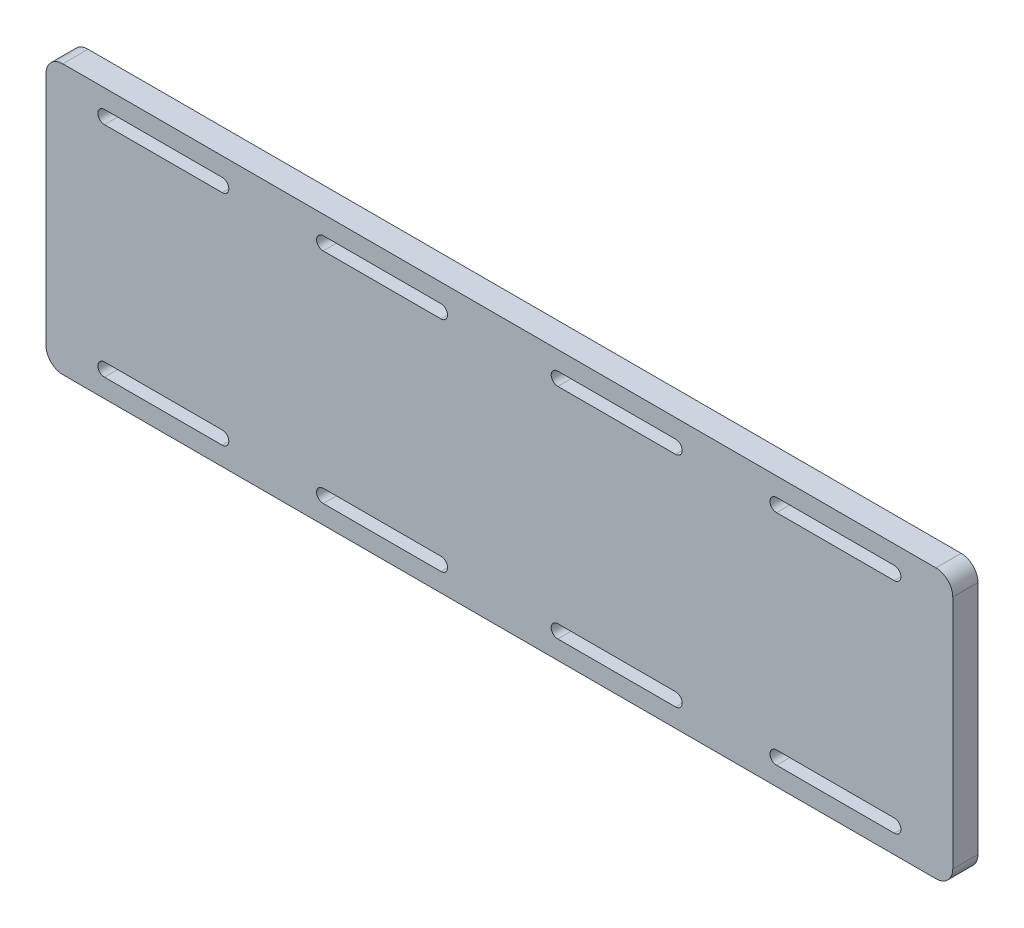
SolidWorks part; units mm, degrees
ref_plane "Front Plane" through (0, 0, 0) normal (0, 0, 1) x (1, 0, 0)
ref_plane "Top Plane" through (0, 0, 0) normal (0, 1, 0) x (1, 0, 0)
ref_plane "Right Plane" through (0, 0, 0) normal (1, 0, 0) x (0, 0, -1)
sketch "Sketch1" plane through (0, 0, 0) normal (0, 0, 1) x (1, 0, 0)
  line L1 (-171.0944, 50.8) -> (171.0944, 50.8)
  line L2 (-171.0944, 50.8) -> (-171.0944, -50.8)
  line L3 (-171.0944, -50.8) -> (171.0944, -50.8)
  line L4 (171.0944, 50.8) -> (171.0944, -50.8)
  line L5 (-171.0944, 50.8) -> (171.0944, -50.8) construction
  line L6 (-171.0944, -50.8) -> (171.0944, 50.8) construction
  point P0 (0, 0)
  dimension "D1" = 101.6
  dimension "D2" = 342.1888
extrude "Boss-Extrude1" add sketch "Sketch1" along normal blind 9.525 contours L1 L4 L3 L2
hole_wizard "#10 Clearance Slot1" positions "Sketch3" profile "Sketch2" size "#10" standard "ANSI Inch" slot yes end condition through all
sketch "Sketch3" plane through (0, 0, 9.525) normal (0, 0, 1) x (1, 0, 0)
  line L0 (-151.5364, -41.275) -> (-102.108, -41.275) construction
  line L2 (-126.8222, 41.275) -> (-44.2722, 41.275)
  line L3 (-126.8222, 41.275) -> (-126.8222, -41.275)
  line L4 (-126.8222, -41.275) -> (-44.2722, -41.275)
  line L5 (-44.2722, 41.275) -> (-44.2722, -41.275)
  line L6 (-126.8222, 41.275) -> (-44.2722, -41.275) construction
  line L7 (-126.8222, -41.275) -> (-44.2722, 41.275) construction
  line L9 (44.2722, 41.275) -> (126.8222, 41.275)
  line L10 (44.2722, 41.275) -> (44.2722, -41.275)
  line L11 (44.2722, -41.275) -> (126.8222, -41.275)
  line L12 (126.8222, 41.275) -> (126.8222, -41.275)
  line L13 (44.2722, 41.275) -> (126.8222, -41.275) construction
  line L14 (44.2722, -41.275) -> (126.8222, 41.275) construction
  line L15 (-85.5472, 0) -> (85.5472, 0) construction
  point P0 (-126.8222, -41.275)
  point P4 (-44.2722, -41.275)
  point P6 (44.2722, -41.275)
  point P8 (126.8222, -41.275)
  point P10 (126.8222, 41.275)
  point P12 (44.2722, 41.275)
  point P14 (-44.2722, 41.275)
  point P16 (-126.8222, 41.275)
  dimension "D1" = 49.4284
  dimension "D2" = 82.55
  dimension "D3" = 82.55
  dimension "D4" = 171.0944
sketch "Sketch2" plane through (-126.8222, -41.275, 9.525) normal (1, 0, 0) x (0, -1, 0)
  line L0 (0, 0) -> (0, 9.525)
  line L1 (0, 9.525) -> (2.4892, 9.525)
  line L2 (2.4892, 9.525) -> (2.4892, 0)
  line L5 (2.4892, 0) -> (0, 0)
  line L11 (0, -6.35) -> (0, 107.95) construction
  dimension "Thru Hole Dia." = 4.9784
  dimension "Thru Hole Depth" = 9.525
fillet "Fillet1" radius 6.35 4 edges at (-171.0944, 50.8, 4.7625) (-171.0944, -50.8, 4.7625) (171.0944, 50.8, 4.7625) (171.0944, -50.8, 4.7625)
equation "\"outer tube diameter\"= 4.486"
equation "\"Mounting screw spacing\"= 3.25"
equation "\"distance between tubes min\"= .5"
equation "\"D2@Sketch1\"=2*\"outer tube diameter\"+\"distance between tubes min\"+\"distance between tube max\""
equation "\"distance between tube max\"= 4"
equation "\"D4@Sketch3\"=\"outer tube diameter\"+(\"distance between tube max\"+\"distance between tubes min\")/2"
